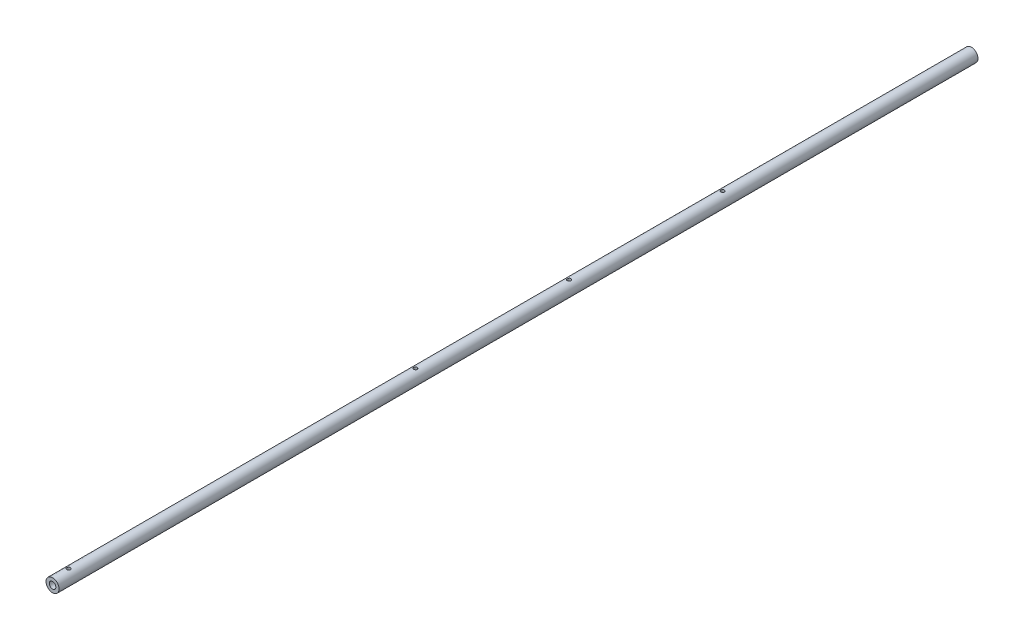
SolidWorks part; units mm, degrees
ref_plane "Front Plane" through (0, 0, 0) normal (0, 0, 1) x (1, 0, 0)
ref_plane "Top Plane" through (0, 0, 0) normal (0, 1, 0) x (1, 0, 0)
ref_plane "Right Plane" through (0, 0, 0) normal (1, 0, 0) x (0, 0, -1)
sketch "Sketch1" plane through (0, 0, 0) normal (0, 0, 1) x (1, 0, 0)
  circle A0 centre (0, 0) radius 3.9306
  circle A1 centre (0, 0) radius 7.8613
  dimension "D1" = 15.7226
  dimension "D2" = 7.8613
extrude "Rod" add sketch "Sketch1" along normal blind 1101.725
sketch "Sketch3" plane through (0, 0, 0) normal (0, 1, 0) x (1, 0, 0)
  line L0 (0, -666.75) -> (0, -1076.325) construction
  line L1 (-7.8613, -1101.725) -> (7.8613, -1101.725) construction
  circle A0 centre (0, -298.45) radius 2.1082
  circle A4 centre (0, -482.6) radius 2.1082
  circle A8 centre (0, -666.75) radius 2.1082
  circle A9 centre (0, -1082.675) radius 2.1082
  dimension "D1" = 4.2164
  dimension "D6" = 4.2164
  dimension "D2" = 298.45
  dimension "D4" = 184.15
  dimension "D5" = 409.575
  dimension "D7" = 19.05
  dimension "D3" = 3
extrude "Holes" cut sketch "Sketch3" against normal through all both and the other way through all
ref_plane "Handle Location" through (0, 0, 1076.325) normal (0, 0, 1) x (1, 0, 0)
equation "\"L\"= 43.375"
equation "\"D1@Rod\" = \"L\""
equation "\"N\"= 3"
equation "\"D3@Sketch3\"=\"N\""
equation "\"S\"= 7.25"
equation "\"D4@Sketch3\"=\"S\""
equation "\"O\"= 11.75"
equation "\"D2@Sketch3\"=\"O\""
equation "\"H\"= 16.125"
equation "\"D5@Sketch3\"=\"H\""
